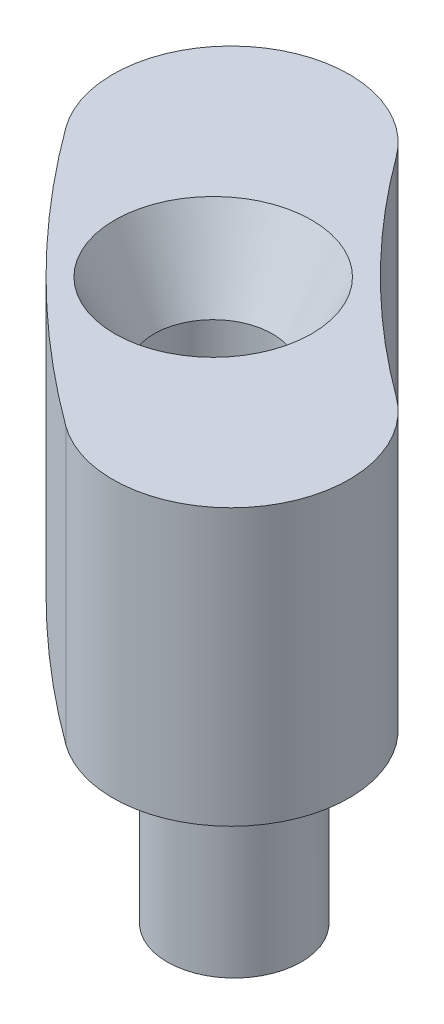
SolidWorks part; units mm, degrees
material "6061 合金"
ref_plane "前视基准面" through (0, 0, 0) normal (0, 0, 1) x (1, 0, 0)
ref_plane "上视基准面" through (0, 0, 0) normal (0, 1, 0) x (1, 0, 0)
ref_plane "右视基准面" through (0, 0, 0) normal (1, 0, 0) x (0, 0, -1)
other "Configuration Table"
sketch "草图1" plane through (0, 0, 0) normal (0, 1, 0) x (1, 0, 0)
  line L0 (-30, 0) -> (30, 0) construction
  line L1 (0, 0) -> (-25.9808, -15) construction
  line L2 (0, 0) -> (0, -30) construction
  line L3 (0, 0) -> (-15, -25.9808) construction
  line L4 (0, 0) -> (-21.5668, -21.5668) construction
  circle A0 centre (0, 0) radius 27.5 construction
  arc A1 (-24.5925, -18.0405) -> (-18.0405, -24.5925) centre (0, 0) ccw
  arc A2 (-19.7546, -14.4915) -> (-14.4915, -19.7546) centre (0, 0) ccw
  circle A3 centre (-19.4454, -19.4454) radius 1.5
  arc A4 (-19.7546, -14.4915) -> (-24.5925, -18.0405) centre (-22.1736, -16.266) ccw
  arc A5 (-14.4915, -19.7546) -> (-18.0405, -24.5925) centre (-16.266, -22.1736) cw
  point P4 (0, 0)
  dimension "D1" = 55
  dimension "D2" = 61
  dimension "D3" = 49
  dimension "D7" = 3
  dimension "D4" = 30
  dimension "D5" = 30
  dimension "D6" = 45
extrude "凸台-拉伸1" add sketch "草图1" along normal blind 7
ref_axis "基准轴1" through (-19.4454, 7, 19.4454) along (0, -1, 0)
ref_plane "基准面2" through (-19.4454, 0, 0) normal (1, 0, 0) x (0, 0, -1)
sketch "草图2" plane through (-19.4454, 0, 0) normal (1, 0, 0) x (0, 0, -1)
  line L0 (-19.4454, 7) -> (-19.4454, 0) construction
  line L1 (-19.4454, 7) -> (-19.4454, 0) construction
  line L3 (-19.4454, 7) -> (-21.9454, 7)
  line L4 (-19.7546, 7) -> (-25.1736, 7) construction
  line L5 (-21.9454, 7) -> (-20.6954, 4.5)
  line L6 (-20.6954, 4.5) -> (-19.4454, 4.5)
  line L7 (-19.4454, 7) -> (-19.4454, 4.5)
  dimension "D1" = 5
  dimension "D2" = 2.5
  dimension "D3" = 2.5
revolve "切除-旋转1" cut sketch "草图2" angle 360 about L0
sketch "草图3" plane through (0, 0, 0) normal (0, -1, 0) x (1, 0, 0)
  line L0 (-19.4454, 19.4454) -> (0, 0) construction
  line L1 (-15.9693, 22.3882) -> (0, 0) construction
  line L2 (-22.3882, 15.9693) -> (0, 0) construction
  circle A0 centre (0, 0) radius 27.5 construction
  circle A1 centre (-15.9693, 22.3882) radius 1.7
  circle A2 centre (-22.3882, 15.9693) radius 2
  dimension "D2" = 3.4
  dimension "D4" = 4
  dimension "D1" = 9.5
  dimension "D3" = 9.5
extrude "凸台-拉伸2" add sketch "草图3" along normal blind 4
